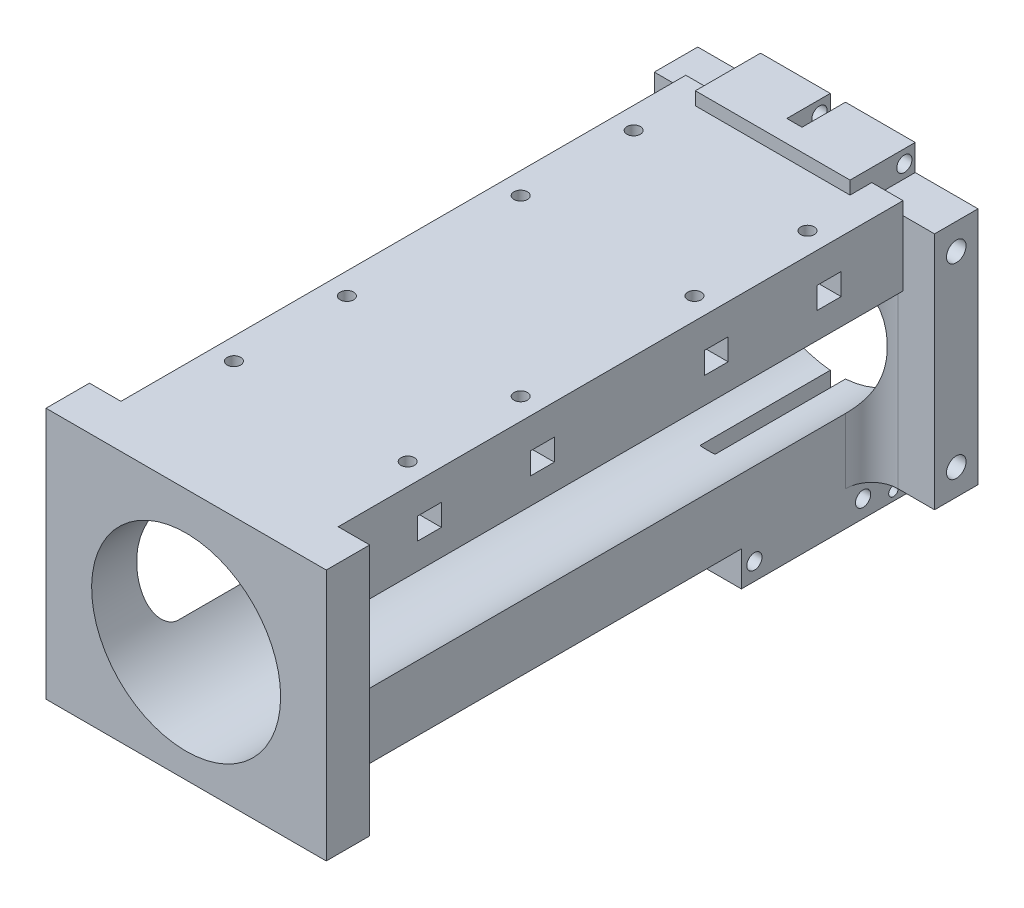
SolidWorks part; units mm, degrees
ref_plane "前视基准面" through (0, 0, 0) normal (0, 0, 1) x (1, 0, 0)
ref_plane "上视基准面" through (0, 0, 0) normal (0, 1, 0) x (1, 0, 0)
ref_plane "右视基准面" through (0, 0, 0) normal (1, 0, 0) x (0, 0, -1)
other "Configuration Table"
sketch "草图1" plane through (0, 0, 0) normal (0, 0, 1) x (1, 0, 0)
  line L1 (-17.8, 27.5) -> (17.8, 27.5)
  line L2 (-17.8, 27.5) -> (-17.8, -27.5)
  line L3 (-17.8, -27.5) -> (17.8, -27.5)
  line L4 (17.8, 27.5) -> (17.8, -27.5)
  line L5 (-17.8, 27.5) -> (17.8, -27.5) construction
  line L6 (-17.8, -27.5) -> (17.8, 27.5) construction
  point P0 (0, 0)
  dimension "D1" = 55
  dimension "D2" = 35.6
extrude "凸台-拉伸1" add sketch "草图1" along normal blind 150
sketch "草图4" plane through (0, 0, 0) normal (0, 0, 1) x (1, 0, 0)
  line L1 (-32.25, 27.5) -> (32.25, 27.5)
  line L2 (-32.25, 27.5) -> (-32.25, -27.5)
  line L3 (-32.25, -27.5) -> (32.25, -27.5)
  line L4 (32.25, 27.5) -> (32.25, -27.5)
  line L5 (-32.25, 27.5) -> (32.25, -27.5) construction
  line L6 (-32.25, -27.5) -> (32.25, 27.5) construction
  point P0 (0, 0)
  dimension "D1" = 64.5
  dimension "D2" = 55
extrude "凸台-拉伸2" add sketch "草图4" along normal blind 10
sketch "草图5" plane through (0, 0, 150) normal (0, 0, 1) x (1, 0, 0)
  line L4 (32.25, 27.5) -> (-32.25, 27.5)
  line L5 (32.25, -27.5) -> (32.25, 27.5)
  line L6 (-32.25, -27.5) -> (32.25, -27.5)
  line L7 (-32.25, 27.5) -> (-32.25, -27.5)
  line L8 (32.25, 27.5) -> (-32.25, 27.5)
  line L9 (32.25, -27.5) -> (32.25, 27.5)
  line L10 (-32.25, -27.5) -> (32.25, -27.5)
  line L11 (-32.25, 27.5) -> (-32.25, -27.5)
  dimension "D1" = 0
extrude "凸台-拉伸3" add sketch "草图5" against normal blind 10
fillet "圆角1" radius 6 4 edges at (-17.8, 0, 10) (-17.8, 0, 140) (17.8, 0, 140) (17.8, 0, 10)
sketch "草图3" plane through (0, 0, 0) normal (0, 0, 1) x (1, 0, 0)
  circle A0 centre (0, 0) radius 21.75
  dimension "D1" = 43.5
extrude "切除-拉伸1" cut sketch "草图3" along normal through all
sketch "草图8" plane through (0, 27.5, 0) normal (0, 1, 0) x (1, 0, 0)
  line L0 (32.25, 0) -> (-32.25, 0) construction
  line L1 (-14, -27) -> (14, -27) construction
  line L2 (-14, -27) -> (-14, -53) construction
  line L3 (-14, -53) -> (14, -53) construction
  line L4 (14, -27) -> (14, -53) construction
  line L5 (-14, -27) -> (14, -53) construction
  line L6 (-14, -53) -> (14, -27) construction
  circle A0 centre (14, -53) radius 1.75
  circle A1 centre (14, -27) radius 1.75
  circle A2 centre (-14, -27) radius 1.75
  circle A3 centre (-14, -53) radius 1.75
  point P0 (0, -40)
  dimension "D4" = 3.5
  dimension "D1" = 28
  dimension "D2" = 26
  dimension "D3" = 27
sketch "草图9" plane through (17.8, 0, 0) normal (1, 0, 0) x (0, 0, -1)
  line L1 (-57, 23.5) -> (-23, 23.5)
  line L2 (-57, 23.5) -> (-57, 18.3)
  line L3 (-57, 18.3) -> (-23, 18.3)
  line L4 (-23, 23.5) -> (-23, 18.3)
  line L5 (-27, 27.5) -> (-53, 27.5) construction
  point P4 (-40, 23.5)
  dimension "D1" = 40
  dimension "D2" = 5.2
  dimension "D3" = 4
  dimension "D4" = 34
extrude "切除-拉伸2" cut sketch "草图9" against normal blind 8
extrude "切除-拉伸3" cut sketch "草图8" against normal blind 5
sketch "草图11" plane through (32.25, 0, 0) normal (1, 0, 0) x (0, 0, -1)
  line L0 (-5, 21.5) -> (-5, -21.5) construction
  line L1 (-10, -27.5) -> (-10, 27.5) construction
  line L3 (-10, -27.5) -> (0, -27.5) construction
  line L4 (-10, 27.5) -> (0, 27.5) construction
  circle A0 centre (-5, 21.5) radius 2.25
  circle A1 centre (-5, -21.5) radius 2.25
  dimension "D1" = 4.5
  dimension "D2" = 5
  dimension "D3" = 6
  dimension "D4" = 6
extrude "切除-拉伸4" cut sketch "草图11" against normal blind 20
sketch "草图12" plane through (0, 0, 0) normal (0, 0, -1) x (-1, 0, 0)
  line L0 (32.25, -27.5) -> (-32.25, -27.5) construction
  line L1 (-23.65, 24.5) -> (-16.85, 24.5)
  line L2 (-23.65, 24.5) -> (-23.65, 17.7)
  line L3 (-23.65, 17.7) -> (-16.85, 17.7)
  line L4 (-16.85, 24.5) -> (-16.85, 17.7)
  line L5 (-23.65, -18.1) -> (-16.85, -18.1)
  line L6 (-23.65, -18.1) -> (-23.65, -24.9)
  line L7 (-23.65, -24.9) -> (-16.85, -24.9)
  line L8 (-16.85, -18.1) -> (-16.85, -24.9)
  line L9 (-32.25, -27.5) -> (-32.25, 27.5) construction
  line L10 (-32.25, 27.5) -> (32.25, 27.5) construction
  point P10 (-23.65, -21.5)
  point P13 (-20.25, -24.9)
  dimension "D1" = 6
  dimension "D2" = 6.8
  dimension "D3" = 6.8
  dimension "D4" = 12
  dimension "D5" = 3
extrude "切除-拉伸5" cut sketch "草图12" against normal blind 10
sketch "草图13" plane through (0, 0, 0) normal (0, 0, -1) x (-1, 0, 0)
  line L0 (32.25, -27.5) -> (-32.25, -27.5) construction
  line L1 (-1.75, -27.5) -> (1.75, -27.5)
  line L2 (-1.75, -27.5) -> (-1.75, -12.5)
  line L3 (-1.75, -12.5) -> (1.75, -12.5)
  line L4 (1.75, -27.5) -> (1.75, -12.5)
  point P6 (0, -12.5)
  dimension "D1" = 3.5
  dimension "D3" = 15
extrude "切除-拉伸6" cut sketch "草图13" against normal blind 30
sketch "草图14" plane through (0, -27.5, 0) normal (0, -1, 0) x (1, 0, 0)
  line L0 (-32.25, 0) -> (-1.75, 0) construction
  line L1 (-17.8, 0) -> (-1.75, 0)
  line L2 (-17.8, 0) -> (-17.8, 40)
  line L3 (-17.8, 40) -> (17.8, 40)
  line L4 (17.8, 0) -> (17.8, 40)
  line L5 (1.75, 0) -> (17.8, 0)
  line L7 (-1.75, 0) -> (-1.75, 30)
  line L8 (-1.75, 30) -> (1.75, 30)
  line L9 (1.75, 0) -> (1.75, 30)
  point P6 (0, 40)
  point P12 (0, 30)
  line M9 (-1.75, 30) -> (1.75, 30)
  line M10 (1.75, 30) -> (1.75, 0)
  line M11 (1.75, 0) -> (32.25, 0)
  line M15 (17.8, 16) -> (17.8, 134)
  line M23 (-17.8, 134) -> (-17.8, 16)
  line M27 (-32.25, 0) -> (-1.75, 0)
  line M28 (-1.75, 0) -> (-1.75, 30)
  dimension "D1" = 35.6
  dimension "D2" = 40
  dimension "D3" = 30
  dimension "D4" = 3.5
extrude "凸台-拉伸5" add sketch "草图14" along normal blind 8 contours L9 L4 L3 L2 L7 L8 M9 M10 M11 M15 M23 M27 M28 | L9 L1 M10 M9 | L1 L7 M9 M28 region at (-17.2645, -27.5, 8)
sketch "草图15" plane through (17.8, 0, 0) normal (1, 0, 0) x (0, 0, -1)
  line L0 (0, -35.5) -> (-40, -35.5) construction
  line L1 (0, -35.5) -> (0, -27.5) construction
  circle A0 centre (-5, -33.5) radius 1.1
  dimension "D3" = 2.2
  dimension "D1" = 2
  dimension "D2" = 5
extrude "切除-拉伸7" cut sketch "草图15" against normal blind 90
sketch "草图16" plane through (17.8, 0, 0) normal (1, 0, 0) x (0, 0, -1)
  line L0 (-37, -31.5) -> (-12, -31.5) construction
  line L1 (-40, -35.5) -> (-40, -27.5) construction
  line L2 (0, -35.5) -> (-40, -35.5) construction
  circle A0 centre (-37, -31.5) radius 1.75
  circle A1 centre (-12, -31.5) radius 1.75
  dimension "D3" = 3.5
  dimension "D1" = 25
  dimension "D2" = 3
  dimension "D4" = 4
extrude "切除-拉伸8" cut sketch "草图16" against normal blind 90
sketch "草图17" plane through (0, 27.5, 0) normal (0, 1, 0) x (1, 0, 0)
  line L0 (32.25, 0) -> (-32.25, 0) construction
  line L1 (-17.8, 0) -> (17.8, 0)
  line L2 (-17.8, 0) -> (-17.8, -15)
  line L3 (-17.8, -15) -> (17.8, -15)
  line L4 (17.8, 0) -> (17.8, -15)
  line L5 (17.8, -134) -> (17.8, -16) construction
  line L6 (-17.8, -134) -> (-17.8, -16) construction
  dimension "D1" = 15
extrude "凸台-拉伸6" add sketch "草图17" along normal blind 6
sketch "草图18" plane through (17.8, 0, 0) normal (1, 0, 0) x (0, 0, -1)
  line L0 (0, 33.5) -> (0, 27.5) construction
  line L1 (-10, 27.5) -> (0, 27.5) construction
  circle A0 centre (-2.5, 30.5) radius 1.75
  dimension "D3" = 3.5
  dimension "D1" = 2.5
  dimension "D2" = 3
extrude "切除-拉伸9" cut sketch "草图18" against normal blind 60
sketch "草图19" plane through (0, 0, 0) normal (0, 0, -1) x (-1, 0, 0)
  line L0 (-17.8, 33.5) -> (17.8, 33.5) construction
  line L1 (-1.75, 33.5) -> (1.75, 33.5)
  line L2 (-1.75, 33.5) -> (-1.75, 20.2474)
  line L3 (-1.75, 20.2474) -> (1.75, 20.2474)
  line L4 (1.75, 33.5) -> (1.75, 20.2474)
  point P6 (0, 20.2474)
  dimension "D1" = 3.5
extrude "切除-拉伸10" cut sketch "草图19" against normal blind 10
mirror "镜向2" about plane through (0, 0, 0) normal (1, 0, 0) of "切除-拉伸5", "切除-拉伸4"
ref_plane "基准面1" through (0, 0, 73) normal (0, 0, 1) x (1, 0, 0)
mirror "镜向6" about plane through (0, 0, 0) normal (1, 0, 0) of "切除-拉伸2"
mirror "镜向7" about plane through (0, 0, 73) normal (0, 0, 1) of "镜向6", "切除-拉伸3"
sketch "草图20" plane through (0, 23.5, 0) normal (0, -1, 0) x (1, 0, 0)
  line L0 (17.8, 0) -> (17.8, 40) construction
  line L1 (17.8, 31.5) -> (9.8, 31.5)
  line L2 (17.8, 31.5) -> (17.8, 48.5)
  line L3 (17.8, 48.5) -> (9.8, 48.5)
  line L4 (9.8, 31.5) -> (9.8, 48.5)
  line L6 (17.8, 73) -> (-17.8, 73) construction
  line L7 (17.8, 134) -> (17.8, 40) construction
  line L8 (-17.8, 134) -> (-17.8, 40) construction
  line L9 (0, 40) -> (0, 98.6142) construction
  line L10 (-17.8, 40) -> (17.8, 40) construction
  line L11 (-9.8, 31.5) -> (-9.8, 48.5)
  line L12 (-17.8, 48.5) -> (-9.8, 48.5)
  line L13 (-17.8, 31.5) -> (-17.8, 48.5)
  line L14 (-17.8, 31.5) -> (-9.8, 31.5)
  line L15 (1.75, 0) -> (17.8, 0) construction
  line L16 (-17.8, 114.5) -> (-9.8, 114.5)
  line L17 (-17.8, 114.5) -> (-17.8, 97.5)
  line L18 (-17.8, 97.5) -> (-9.8, 97.5)
  line L19 (-9.8, 114.5) -> (-9.8, 97.5)
  line L20 (9.8, 114.5) -> (9.8, 97.5)
  line L21 (17.8, 97.5) -> (9.8, 97.5)
  line L22 (17.8, 114.5) -> (17.8, 97.5)
  line L23 (17.8, 114.5) -> (9.8, 114.5)
  circle A0 centre (14, 27) radius 1.75 construction
  circle A1 centre (14, 53) radius 1.75 construction
  dimension "D1" = 8
  dimension "D2" = 4.5
  dimension "D3" = 4.5
  dimension "D4" = 73
extrude "凸台-拉伸7" add sketch "草图20" along normal blind 8
sketch "草图22" plane through (0, 0, 0) normal (1, 0, 0) x (0, 0, -1)
  line L0 (-10, 27.5) -> (-10, -27.5) construction
  line L1 (-140, 27.5) -> (-10, 27.5)
  line L2 (-140, 27.5) -> (-140, 12.4989)
  line L3 (-140, 12.4989) -> (-10, 12.4989)
  line L4 (-10, 27.5) -> (-10, 12.4989)
  line L5 (-16, 12.4989) -> (-134, 12.4989) construction
extrude "凸台-拉伸8" add sketch "草图22" along normal mid plane 50
sketch "草图21" plane through (0, 0, 150) normal (0, 0, 1) x (1, 0, 0)
  circle A0 centre (0, 0) radius 21.75
  dimension "D1" = 43.5
extrude "切除-拉伸11" cut sketch "草图21" against normal through all both and the other way through all
sketch "草图23" plane through (0, 27.5, 0) normal (0, 1, 0) x (1, 0, 0)
  line L0 (-25, -15) -> (25, -15)
  line L16 (32.25, 0) -> (17.8, 0)
  line L17 (17.8, 0) -> (17.8, -15)
  line L18 (17.8, -15) -> (-17.8, -15)
  line L19 (-17.8, -15) -> (-17.8, 0)
  line L20 (-17.8, 0) -> (-32.25, 0)
  line L21 (-32.25, 0) -> (-32.25, -10)
  line L22 (-32.25, -10) -> (-25, -10)
  line L23 (-25, -10) -> (-25, -140)
  line L24 (-25, -140) -> (-32.25, -140)
  line L25 (-32.25, -140) -> (-32.25, -150)
  line L26 (-32.25, -150) -> (32.25, -150)
  line L27 (32.25, -150) -> (32.25, -140)
  line L28 (32.25, -140) -> (25, -140)
  line L29 (25, -140) -> (25, -10)
  line L30 (25, -10) -> (32.25, -10)
  line L31 (32.25, -10) -> (32.25, 0)
  line L39 (-25, -15) -> (-25, -140)
  line L40 (-25, -140) -> (-32.25, -140)
  line L41 (-32.25, -140) -> (-32.25, -150)
  line L42 (-32.25, -150) -> (32.25, -150)
  line L43 (32.25, -150) -> (32.25, -140)
  line L44 (32.25, -140) -> (25, -140)
  line L45 (25, -140) -> (25, -15)
  dimension "D1" = 0
extrude "凸台-拉伸9" add sketch "草图23" along normal blind 3
sketch "草图24" plane through (0, 30.5, 0) normal (0, 1, 0) x (1, 0, 0)
  line L0 (32.25, -10) -> (25, -10) construction
  line L1 (-20, -27) -> (20, -27) construction
  line L2 (-20, -27) -> (-20, -53) construction
  line L3 (-20, -53) -> (20, -53) construction
  line L4 (20, -27) -> (20, -53) construction
  line L6 (-20, -93) -> (20, -93) construction
  line L7 (-20, -93) -> (-20, -119) construction
  line L8 (-20, -119) -> (20, -119) construction
  line L9 (20, -93) -> (20, -119) construction
  circle A0 centre (-20, -93) radius 1.55
  circle A1 centre (-20, -119) radius 1.55
  circle A2 centre (20, -93) radius 1.55
  circle A3 centre (20, -119) radius 1.55
  circle A4 centre (20, -53) radius 1.55
  circle A5 centre (-20, -53) radius 1.55
  circle A6 centre (-20, -27) radius 1.55
  circle A7 centre (20, -27) radius 1.55
  point P4 (0, -27)
  dimension "D5" = 3.1
  dimension "D1" = 17
  dimension "D2" = 26
  dimension "D3" = 40
  dimension "D4" = 40
extrude "切除-拉伸12" cut sketch "草图24" against normal blind 12
ref_plane "基准面2" through (0, 23.5, 0) normal (0, 1, 0) x (1, 0, 0)
sketch "草图25" plane through (0, 23.5, 0) normal (0, 1, 0) x (1, 0, 0)
  line L0 (25, -140) -> (25, -15) construction
  line L1 (16.8, -24.25) -> (25, -24.25)
  line L2 (16.8, -24.25) -> (16.8, -29.75)
  line L3 (16.8, -29.75) -> (25, -29.75)
  line L4 (25, -24.25) -> (25, -29.75)
  line L5 (0, -53.4865) -> (0, 0) construction
  line L6 (-9.187, -40) -> (7.0869, -40) construction
  line L7 (25, -55.75) -> (25, -50.25)
  line L8 (16.8, -50.25) -> (25, -50.25)
  line L9 (16.8, -55.75) -> (16.8, -50.25)
  line L10 (16.8, -55.75) -> (25, -55.75)
  line L11 (-25, -24.25) -> (-25, -29.75)
  line L12 (-16.8, -29.75) -> (-25, -29.75)
  line L13 (-16.8, -24.25) -> (-16.8, -29.75)
  line L14 (-16.8, -24.25) -> (-25, -24.25)
  line L15 (-16.8, -55.75) -> (-25, -55.75)
  line L16 (-16.8, -55.75) -> (-16.8, -50.25)
  line L17 (-16.8, -50.25) -> (-25, -50.25)
  line L18 (-25, -55.75) -> (-25, -50.25)
  line L19 (-18.7131, -73) -> (17.9362, -73) construction
  line L20 (-25, -90.25) -> (-25, -95.75)
  line L21 (-16.8, -95.75) -> (-25, -95.75)
  line L22 (-16.8, -90.25) -> (-16.8, -95.75)
  line L23 (-16.8, -90.25) -> (-25, -90.25)
  line L24 (-16.8, -121.75) -> (-25, -121.75)
  line L25 (-16.8, -121.75) -> (-16.8, -116.25)
  line L26 (-16.8, -116.25) -> (-25, -116.25)
  line L27 (-25, -121.75) -> (-25, -116.25)
  line L28 (16.8, -90.25) -> (25, -90.25)
  line L29 (16.8, -90.25) -> (16.8, -95.75)
  line L30 (16.8, -95.75) -> (25, -95.75)
  line L31 (25, -90.25) -> (25, -95.75)
  line L32 (25, -121.75) -> (25, -116.25)
  line L33 (16.8, -116.25) -> (25, -116.25)
  line L34 (16.8, -121.75) -> (16.8, -116.25)
  line L35 (16.8, -121.75) -> (25, -121.75)
  circle A0 centre (20, -27) radius 1.55 construction
  circle A1 centre (20, -27) radius 1.55 construction
  circle A2 centre (20, -53) radius 1.55 construction
  dimension "D1" = 5.5
  dimension "D2" = 2.75
  dimension "D3" = 3.2
  dimension "D4" = 13
  dimension "D5" = 20
extrude "切除-拉伸13" cut sketch "草图25" against normal blind 5
sketch "草图26" plane through (0, 27.5, 0) normal (0, 1, 0) x (1, 0, 0)
  line L0 (17.8, -15) -> (17.8, 0) construction
  line L1 (25, -15) -> (17.8, -15)
  line L2 (25, -15) -> (25, -10)
  line L3 (25, -10) -> (17.8, -10)
  line L4 (17.8, -15) -> (17.8, -10)
  line L6 (-17.8, -15) -> (-25, -15)
  line L7 (-17.8, -15) -> (-17.8, -10)
  line L8 (-17.8, -10) -> (-25, -10)
  line L9 (-25, -15) -> (-25, -10)
extrude "凸台-拉伸10" add sketch "草图26" along normal blind 3
